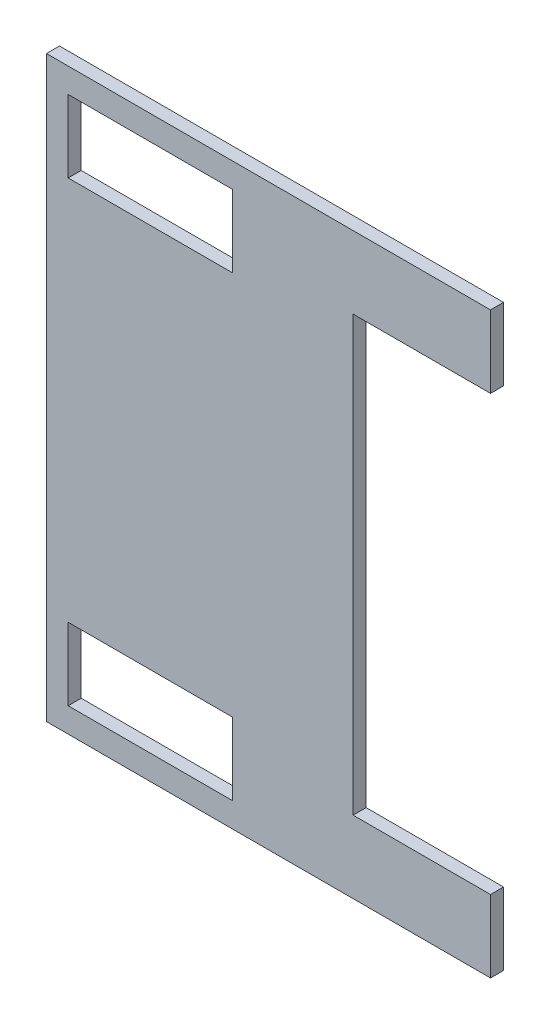
SolidWorks part; units mm, degrees
material "Pine"
ref_plane "Front Plane" through (0, 0, 0) normal (0, 0, 1) x (1, 0, 0)
ref_plane "Top Plane" through (0, 0, 0) normal (0, 1, 0) x (1, 0, 0)
ref_plane "Right Plane" through (0, 0, 0) normal (1, 0, 0) x (0, 0, -1)
sketch "Sketch1" plane through (0, 0, 0) normal (0, 0, 1) x (1, 0, 0)
  line L0 (-16.8129, -74.6) -> (-16.8129, 325.4)
  line L1 (-16.8129, 325.4) -> (-323.8122, 325.4)
  line L2 (-323.8122, 325.4) -> (-323.8122, -74.6)
  line L3 (-323.8122, -74.6) -> (-16.8129, -74.6)
  line L9 (-308.8122, 308.4) -> (-195.1729, 308.4)
  line L10 (-308.8122, 308.4) -> (-308.8122, 258.4)
  line L11 (-308.8122, 258.4) -> (-195.1729, 258.4)
  line L12 (-195.1729, 308.4) -> (-195.1729, 258.4)
  line L13 (-308.8122, 308.4) -> (-195.1729, 258.4) construction
  line L14 (-308.8122, 258.4) -> (-195.1729, 308.4) construction
  line L18 (-308.8122, -57.6) -> (-195.1729, -57.6)
  line L19 (-308.8122, -57.6) -> (-308.8122, -7.6)
  line L20 (-308.8122, -7.6) -> (-195.1729, -7.6)
  line L21 (-195.1729, -57.6) -> (-195.1729, -7.6)
  line L22 (-308.8122, -57.6) -> (-195.1729, -7.6) construction
  line L23 (-308.8122, -7.6) -> (-195.1729, -57.6) construction
  point P16 (-251.9926, 283.4)
  point P27 (-251.9926, -32.6)
  dimension "D2" = 50
  dimension "D3" = 17
  dimension "D5" = 15
  dimension "D6" = 15
extrude "Boss-Extrude1" add sketch "Sketch1" along normal blind 9
sketch "Sketch2" plane through (0, 0, 0) normal (0, 0, -1) x (-1, 0, 0)
  line L0 (111.8129, -24.6) -> (111.8129, 275.4)
  line L1 (16.8129, 325.4) -> (111.8129, 325.4)
  line L2 (16.8129, 325.4) -> (16.8129, 275.4)
  line L3 (16.8129, 275.4) -> (111.8129, 275.4)
  line L4 (111.8129, 325.4) -> (111.8129, 275.4)
  line L5 (16.8129, 325.4) -> (111.8129, 275.4) construction
  line L6 (16.8129, 275.4) -> (111.8129, 325.4) construction
  line L7 (16.8129, -74.6) -> (111.8129, -74.6)
  line L8 (16.8129, -74.6) -> (16.8129, -24.6)
  line L9 (16.8129, -24.6) -> (111.8129, -24.6)
  line L10 (111.8129, -74.6) -> (111.8129, -24.6)
  line L11 (16.8129, -74.6) -> (111.8129, -24.6) construction
  line L12 (16.8129, -24.6) -> (111.8129, -74.6) construction
  point P4 (64.3129, 300.4)
  point P10 (64.3129, -49.6)
  line M11 (16.8129, 325.4) -> (16.8129, -74.6)
  dimension "D1" = 50
  dimension "D2" = 50
  dimension "D3" = 95
extrude "Cut-Extrude1" cut sketch "Sketch2" against normal through all contours L9 L0 L3 M11 region at (-64.3129, 125.4, 0)
